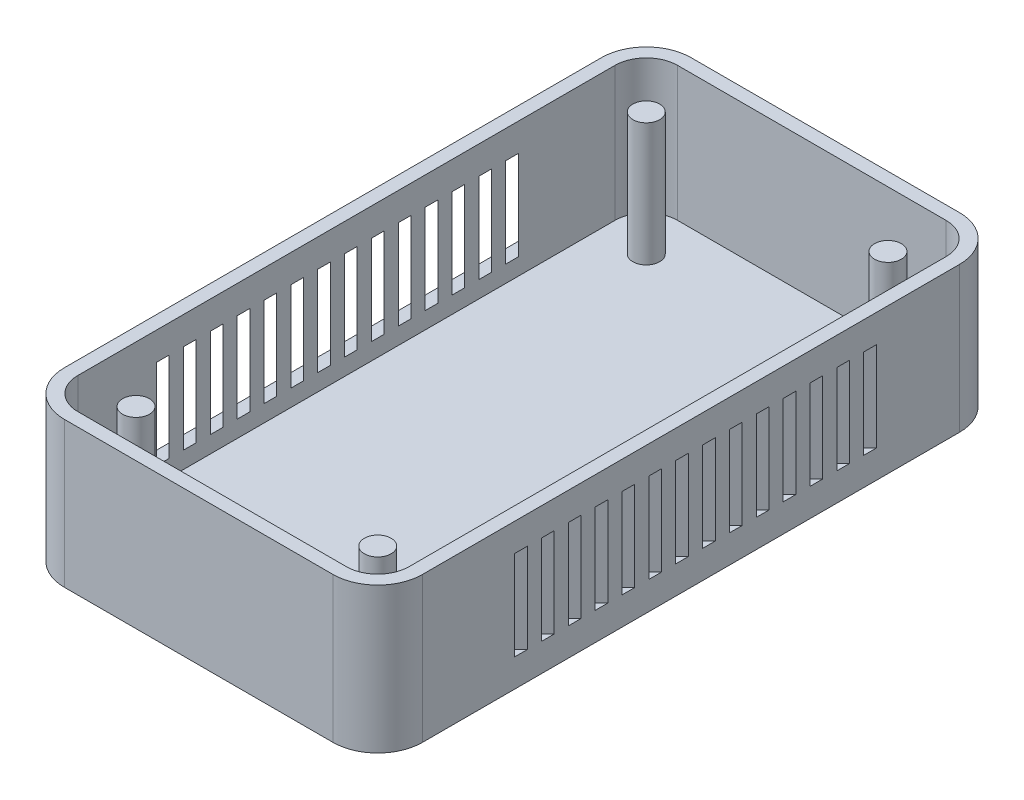
SolidWorks part; units mm, degrees
ref_plane "Front Plane" through (0, 0, 0) normal (0, 0, 1) x (1, 0, 0)
ref_plane "Top Plane" through (0, 0, 0) normal (0, 1, 0) x (1, 0, 0)
ref_plane "Right Plane" through (0, 0, 0) normal (1, 0, 0) x (0, 0, -1)
sketch "Sketch1" plane through (0, 0, 0) normal (0, 1, 0) x (1, 0, 0)
  line L0 (-37, 60) -> (-37, -60)
  line L1 (-30, 70) -> (30, 70)
  line L2 (-40, 60) -> (-40, -60)
  line L3 (-30, -70) -> (30, -70)
  line L4 (40, 60) -> (40, -60)
  line L5 (-40, 70) -> (40, -70) construction
  line L6 (-40, -70) -> (40, 70) construction
  line L7 (-30, -67) -> (30, -67)
  line L8 (37, 60) -> (37, -60)
  line L9 (-30, 67) -> (30, 67)
  line L10 (0, 70) -> (0, -70) construction
  line L11 (40, 0) -> (-40, 0) construction
  arc A0 (-40, -60) -> (-30, -70) centre (-30, -60) ccw
  arc A1 (30, -70) -> (40, -60) centre (30, -60) ccw
  arc A2 (30, 70) -> (40, 60) centre (30, 60) cw
  arc A3 (-30, 70) -> (-40, 60) centre (-30, 60) ccw
  arc A4 (-37, -60) -> (-30, -67) centre (-30, -60) ccw
  arc A5 (30, -67) -> (37, -60) centre (30, -60) ccw
  arc A6 (30, 67) -> (37, 60) centre (30, 60) cw
  arc A7 (-30, 67) -> (-37, 60) centre (-30, 60) ccw
  circle A8 centre (0, -27) radius 12.5
  circle A9 centre (0, -27) radius 15.5
  circle A10 centre (27, -57) radius 3
  circle A11 centre (-27, -57) radius 3
  circle A12 centre (-27, 57) radius 3
  circle A13 centre (27, 57) radius 3
  point P0 (0, 0)
  dimension "D3" = 10
  dimension "D5" = 25
  dimension "D6" = 40
  dimension "D8" = 6
  dimension "D9" = 13
  dimension "D10" = 13
  dimension "D1" = 80
  dimension "D2" = 140
  dimension "D4" = 3
  dimension "D7" = 3
extrude "Boss-Extrude1" add sketch "Sketch1" along normal blind 2.5 contours L2 A0 L3 A1 L4 A2 L1 A3
extrude "Boss-Extrude2" add sketch "Sketch1<3>" along normal blind 30 from surface contours L4 A1 L3 A0 L2 A3 L1 A2 | L8 A5 L7 A4 L0 A7 L9 A6 starting at face at (0, 2.5, 0)
sketch "Sketch1<3>" plane through (0, 0, 0) normal (0, 1, 0) x (1, 0, 0) same geometry as "Sketch1"
extrude "Boss-Extrude4" add sketch "Sketch1<5>" along normal blind 30 contours A10 | A11 | A13 | A12
sketch "Sketch1<5>" plane through (0, 0, 0) normal (0, 1, 0) x (1, 0, 0) same geometry as "Sketch1"
ref_plane "Plane1" through (0, 16.25, 0) normal (0, 1, 0) x (1, 0, 0)
sketch "Sketch5" plane through (0, 16.25, 0) normal (0, 1, 0) x (1, 0, 0)
  line L0 (37, 37) -> (-37, -37) construction
  line L1 (37, -60) -> (37, 60) construction
  line L2 (-37, -60) -> (-37, 60) construction
  line L4 (30, 70) -> (-30, 70) construction
  dimension "D1" = 45
  dimension "D2" = 33
ref_plane "Plane2" through (37, 16.25, -37) normal (-0.7071, 0, 0.7071) x (0.7071, 0, 0.7071)
sketch "Sketch8" plane through (37, 16.25, -37) normal (-0.7071, 0, 0.7071) x (0.7071, 0, 0.7071)
  line L1 (1, 10) -> (-1, 10)
  line L2 (1, 10) -> (1, -10)
  line L3 (1, -10) -> (-1, -10)
  line L4 (-1, 10) -> (-1, -10)
  line L5 (1, 10) -> (-1, -10) construction
  line L6 (1, -10) -> (-1, 10) construction
  point P0 (0, 0)
  dimension "D1" = 20
  dimension "D2" = 2
  dimension "D4" = 0
extrude "Cut-Extrude3" cut sketch "Sketch8" against normal up to next and the other way up to next
sketch "Sketch9" plane through (40, 0, 0) normal (1, 0, 0) x (0, 0, -1)
  line L0 (-60, 16.25) -> (60, 16.25) construction
  line L1 (-60, 32.5) -> (-60, 0) construction
  line L2 (60, 32.5) -> (60, 0) construction
pattern_linear "LPattern1" count 14 spacing 6 along (0, 0, 1) of "Cut-Extrude3"
mirror "Mirror2" about plane through (0, 0, 0) normal (1, 0, 0) of "LPattern1"
